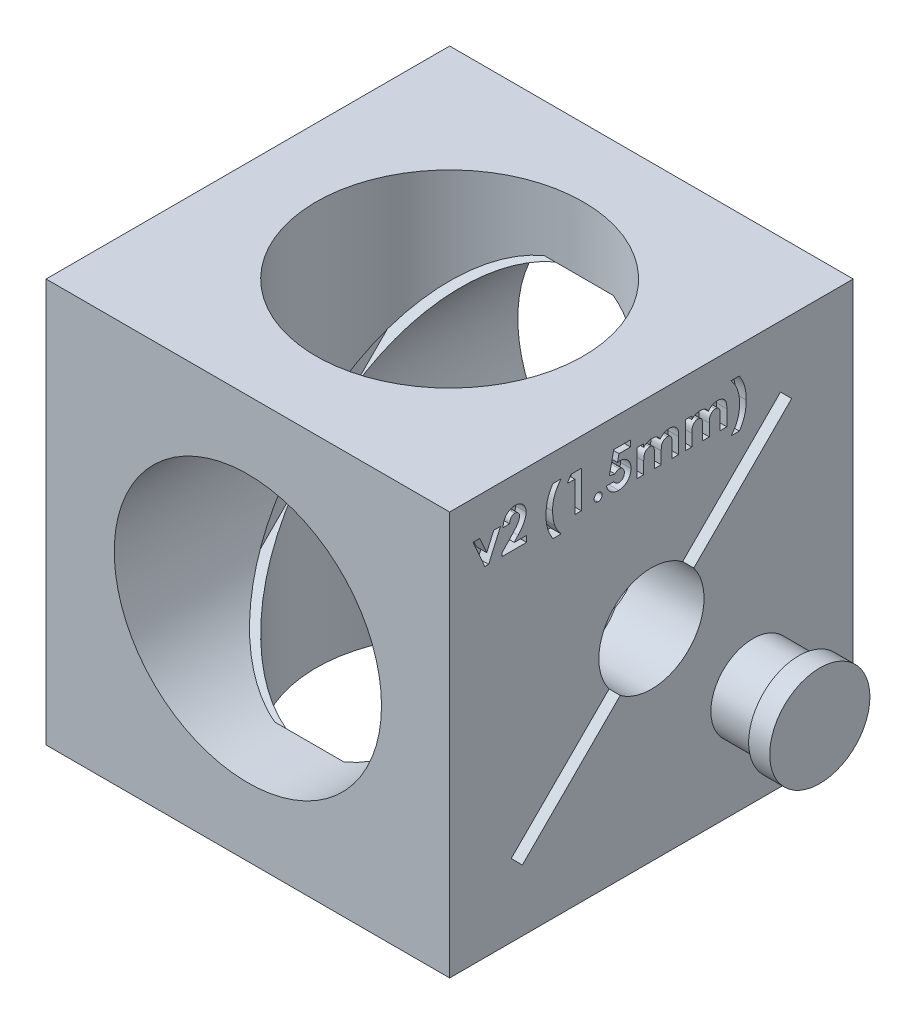
SolidWorks part; units mm, degrees
ref_plane "Front Plane" through (0, 0, 0) normal (0, 0, 1) x (1, 0, 0)
ref_plane "Top Plane" through (0, 0, 0) normal (0, 1, 0) x (1, 0, 0)
ref_plane "Right Plane" through (0, 0, 0) normal (1, 0, 0) x (0, 0, -1)
sketch "Sketch1" plane through (0, 0, 0) normal (0, 1, 0) x (1, 0, 0)
  line L1 (-19.177, -19.177) -> (19.177, -19.177)
  line L2 (-19.177, -19.177) -> (-19.177, 19.177)
  line L3 (-19.177, 19.177) -> (19.177, 19.177)
  line L4 (19.177, -19.177) -> (19.177, 19.177)
  line L5 (-19.177, -19.177) -> (19.177, 19.177) construction
  line L6 (-19.177, 19.177) -> (19.177, -19.177) construction
  point P0 (0, 0)
  dimension "D1" = 38.354
  dimension "D2" = 38.354
extrude "Boss-Extrude1" add sketch "Sketch1" along normal mid plane 38.354
sketch "Sketch2" plane through (0, 0, 0) normal (0, 0, 1) x (1, 0, 0)
  circle A0 centre (0, 0) radius 12.7
  dimension "D1" = 25.4
extrude "Cut-Extrude1" cut sketch "Sketch2" against normal through all both and the other way through all
sketch "Sketch3" plane through (0, 19.177, 0) normal (0, -1, 0) x (0, 0, -1)
  circle A0 centre (0, 0) radius 12.7
  dimension "D1" = 25.4
extrude "Cut-Extrude3" cut sketch "Sketch3" against normal through all and the other way through all
sketch "Sketch4" plane through (0, 0, 0) normal (1, 0, 0) x (0, 0, -1)
  line L0 (-19.177, -19.177) -> (19.177, 19.177) construction
  line L1 (-12.2683, -13.329) -> (13.329, 12.2683)
  line L2 (-12.2683, -13.329) -> (-13.329, -12.2683)
  line L3 (-13.329, -12.2683) -> (12.2683, 13.329)
  line L4 (13.329, 12.2683) -> (12.2683, 13.329)
  line L5 (-12.2683, -13.329) -> (12.2683, 13.329) construction
  line L6 (-13.329, -12.2683) -> (13.329, 12.2683) construction
  line L7 (19.177, 19.177) -> (19.177, -19.177) construction
  point P0 (0, 0)
  point P12 (-12.7986, -12.7986)
  dimension "D1" = 1.5
  dimension "D2" = 36.2
extrude "Cut-Extrude4" cut sketch "Sketch4" against normal mid plane 25
extrude "Cut-Extrude5" cut sketch "Sketch4<2>" along normal through all
sketch "Sketch4<2>" plane through (0, 0, 0) normal (1, 0, 0) x (0, 0, -1) same geometry as "Sketch4"
sketch "Sketch5" plane through (19.177, 0, 0) normal (1, 0, 0) x (0, 0, -1)
  circle A0 centre (0, 0) radius 5
  dimension "D1" = 10
extrude "Cut-Extrude6" cut sketch "Sketch5" against normal blind 10
sketch "Sketch6" plane through (19.177, 0, 0) normal (1, 0, 0) x (0, 0, -1)
  line L0 (-16.976, 13.0164) -> (14.0771, 13.0164) construction
  line L1 (4.0259, 2.9652) -> (13.329, 12.2683) construction
  text T0 "<b>v2 (1.5mm)</b>"
  point P3 (12.5108, 11.4502)
extrude "Cut-Extrude7" cut sketch "Sketch6" against normal blind 1
sketch "Sketch7" plane through (19.177, 0, 0) normal (1, 0, 0) x (0, 0, -1)
  line L0 (-19.177, -19.177) -> (19.177, -19.177) construction
  line L1 (19.177, 19.177) -> (19.177, -19.177) construction
  circle A0 centre (9.652, -9.652) radius 4
  dimension "D1" = 8
  dimension "D2" = 9.525
  dimension "D3" = 9.525
extrude "Boss-Extrude2" add sketch "Sketch7" along normal blind 6.35
sketch "Sketch8" plane through (25.527, 0, 0) normal (1, 0, 0) x (0, 0, -1)
  circle A0 centre (9.652, -9.652) radius 4.7625
  dimension "D1" = 9.525
extrude "Boss-Extrude3" add sketch "Sketch8" against normal blind 2
